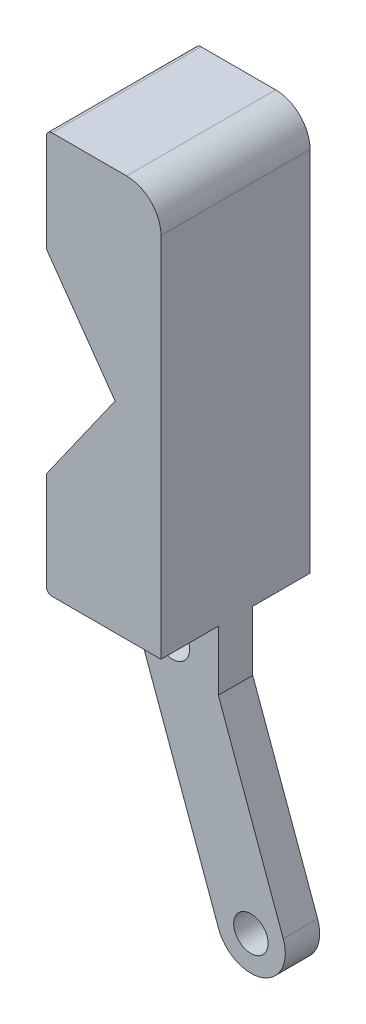
SolidWorks part; units mm, degrees
material "3.0205 (EN-AW 1200)"
ref_plane "Piano frontale" through (0, 0, 0) normal (0, 0, 1) x (1, 0, 0)
ref_plane "Piano superiore" through (0, 0, 0) normal (0, 1, 0) x (1, 0, 0)
ref_plane "Piano destro" through (0, 0, 0) normal (1, 0, 0) x (0, 0, -1)
sketch "Schizzo2" plane through (0, 0, 0) normal (0, 0, 1) x (1, 0, 0)
  line L0 (0, 0) -> (-6.8404, 18.7939) construction
  line L1 (-6.8404, -8.011) -> (-6.8404, 56.7939) construction
  line L2 (-2.8191, -1.0261) -> (-9.6595, 17.7678)
  line L3 (2.8191, 1.0261) -> (-4.0213, 19.8199)
  line L5 (-2.8404, 15.7939) -> (-2.8404, 56.7939)
  line L6 (-9.8404, 18.7939) -> (-9.8404, 56.7939) construction
  line L7 (-2.8404, 56.7939) -> (-12.8404, 56.7939)
  line L8 (-12.8404, 56.7939) -> (-12.8404, 47.7939)
  line L9 (-12.8404, 21.7939) -> (-12.8404, 30.7939)
  line L10 (-12.8404, 47.7939) -> (-6.8404, 39.2939)
  line L11 (-12.8404, 30.7939) -> (-6.8404, 39.2939)
  line L12 (-19.445, 0) -> (19.0356, 0) construction
  line L13 (-6.8404, 21.7939) -> (-2.8404, 21.7939)
  line L14 (-6.8404, 21.7939) -> (-12.8404, 21.7939)
  line L15 (-10.3488, 21.7939) -> (-9.8404, 18.7939)
  arc A0 (-2.8191, -1.0261) -> (2.8191, 1.0261) centre (0, 0) ccw
  arc A1 (-4.0213, 19.8199) -> (-9.6595, 17.7678) centre (-6.8404, 18.7939) ccw
  circle A2 centre (-6.8404, 18.7939) radius 1.5
  circle A3 centre (0, 0) radius 1.5
  point P4 (-3.4202, 9.3969)
  point P23 (-6.8404, 56.7939)
  dimension "D3" = 3
  dimension "D4" = 3
  dimension "D1" = 20
  dimension "D2" = 6
  dimension "D5" = 41
  dimension "D6" = 10
  dimension "D7" = 9
  dimension "D8" = 4
  dimension "D9" = 8.5
  dimension "D10" = 9
  dimension "D11" = 80.381
  dimension "D12" = 70
extrude "Estrusione-Estrusione1" add sketch "Schizzo2" along normal blind 1.5 and the other way blind 1.5 contours L3 A1 L2 A0 A3 A2 | A1 L3 L5 L13 | A1 L14 L15 region at (-3.4202, 9.3969, 0) region at (-9.408, 21.0304, 0) region at (-3.6915, 20.2383, 0)
extrude "Estrusione-Estrusione2" add sketch "Schizzo2<10>" along normal blind 6.5 and the other way blind 6.5 contours L14 L13 L5 L7 L8 L10 L11 L9 region at (-11.5946, 22.1579, 0)
sketch "Schizzo2<10>" plane through (0, 0, 0) normal (0, 0, 1) x (1, 0, 0) same geometry as "Schizzo2"
fillet "Raccordo1" radius 3 1 edges at (-2.8404, 56.7939, 0)
fillet "Raccordo2" radius 0.5 1 edges at (-12.8404, 21.7939, 0)
fillet "Raccordo3" radius 0.5 1 edges at (-12.8404, 56.7939, 0)
